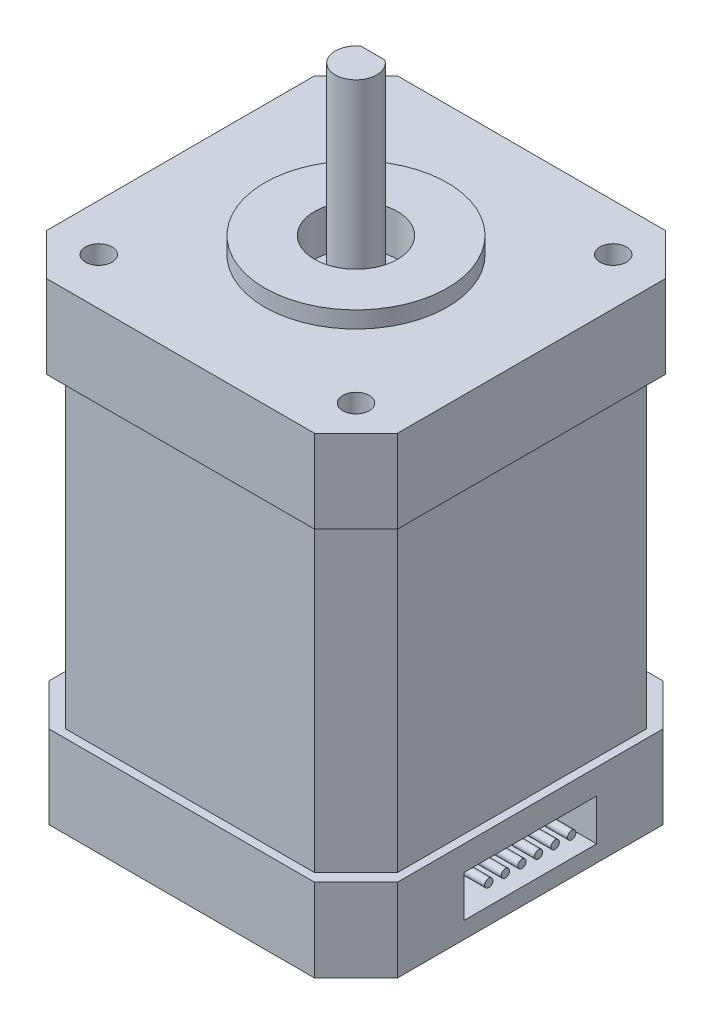
SolidWorks part; units mm, degrees
ref_plane "前视基准面" through (0, 0, 0) normal (0, 0, 1) x (1, 0, 0)
ref_plane "上视基准面" through (0, 0, 0) normal (0, 1, 0) x (1, 0, 0)
ref_plane "右视基准面" through (0, 0, 0) normal (1, 0, 0) x (0, 0, -1)
sketch "草图1" plane through (0, 0, 0) normal (0, 1, 0) x (1, 0, 0)
  line L1 (-21.15, 21.15) -> (21.15, 21.15)
  line L2 (-21.15, 21.15) -> (-21.15, -21.15)
  line L3 (-21.15, -21.15) -> (21.15, -21.15)
  line L4 (21.15, 21.15) -> (21.15, -21.15)
  dimension "D1" = 42.3
  dimension "D2" = 42.3
  dimension "D3" = 21.15
  dimension "D4" = 21.15
extrude "凸台-拉伸1" add sketch "草图1" along normal blind 10
chamfer "倒角1" distance 5 angle 45 4 edges at (-21.15, 5, -21.15) (-21.15, 5, 21.15) (21.15, 5, 21.15) (21.15, 5, -21.15)
sketch "草图2" plane through (0, 10, 0) normal (0, 1, 0) x (1, 0, 0)
  circle A0 centre (-15.5, -15.5) radius 1.6
  circle A1 centre (15.5, -15.5) radius 1.6
  circle A2 centre (15.5, 15.5) radius 1.6
  circle A3 centre (-15.5, 15.5) radius 1.6
  dimension "D1" = 31
  dimension "D2" = 31
extrude "切除-拉伸1" cut sketch "草图2" against normal blind 10
sketch "草图3" plane through (0, 0, 0) normal (0, -1, 0) x (1, 0, 0)
  line L1 (20, 20) -> (-20, 20)
  line L2 (20, 20) -> (20, -20)
  line L3 (20, -20) -> (-20, -20)
  line L4 (-20, 20) -> (-20, -20)
  dimension "D1" = 40
  dimension "D2" = 40
  dimension "D3" = 20
  dimension "D4" = 20
extrude "凸台-拉伸2" add sketch "草图3" along normal blind 37
chamfer "倒角2" distance 5 angle 45 4 edges at (20, -18.5, 20) (-20, -18.5, 20) (-20, -18.5, -20) (20, -18.5, -20)
sketch "草图4" plane through (0, -37, 0) normal (0, -1, 0) x (1, 0, 0)
  line L1 (21, 21) -> (-21, 21)
  line L2 (21, 21) -> (21, -21)
  line L3 (21, -21) -> (-21, -21)
  line L4 (-21, 21) -> (-21, -21)
  dimension "D1" = 42
  dimension "D2" = 42
  dimension "D3" = 21
  dimension "D4" = 21
extrude "凸台-拉伸3" add sketch "草图4" along normal blind 10
chamfer "倒角3" distance 5 angle 45 4 edges at (-21, -42, 21) (21, -42, 21) (21, -42, -21) (-21, -42, -21)
sketch "草图5" plane through (0, 10, 0) normal (0, 1, 0) x (1, 0, 0)
  circle A0 centre (0, 0) radius 11
extrude "凸台-拉伸4" add sketch "草图5" along normal blind 2
sketch "草图6" plane through (0, 12, 0) normal (0, 1, 0) x (1, 0, 0)
  circle A0 centre (0, 0) radius 5
extrude "切除-拉伸2" cut sketch "草图6" against normal blind 5
sketch "草图7" plane through (0, 7, 0) normal (0, 1, 0) x (1, 0, 0)
  line L0 (-1.4339, 2.0479) -> (1.4339, 2.0479)
  arc A0 (-1.4339, 2.0479) -> (1.4339, 2.0479) centre (0, 0) ccw
extrude "凸台-拉伸5" add sketch "草图7" along normal blind 23
sketch "草图8" plane through (0, -47, 0) normal (0, -1, 0) x (1, 0, 0)
  circle A0 centre (0, 0) radius 5
extrude "切除-拉伸3" cut sketch "草图8" against normal blind 3
sketch "草图9" plane through (21, 0, 0) normal (1, 0, 0) x (0, 0, -1)
  line L5 (16, -47) -> (16, -37) construction
  line L6 (-8, -40) -> (8, -40)
  line L8 (-8, -40) -> (-8, -45)
  line L9 (-8, -45) -> (8, -45)
  line L10 (8, -40) -> (8, -45)
  line L11 (16, -47) -> (-16, -47) construction
  point P4 (8, -42.5)
  point P7 (0, -45)
  dimension "D1" = 5
  dimension "D2" = 16
  dimension "D3" = 8
  dimension "D4" = 2
extrude "切除-拉伸5" cut sketch "草图9" against normal blind 5
sketch "草图10" plane through (16, 0, 0) normal (1, 0, 0) x (0, 0, -1)
  line L0 (8, -45) -> (8, -40) construction
  circle A0 centre (-5, -42.5764) radius 0.5
  circle A1 centre (-3, -42.5764) radius 0.5
  circle A2 centre (-1, -42.5764) radius 0.5
  circle A3 centre (1, -42.5764) radius 0.5
  circle A4 centre (3, -42.5764) radius 0.5
  circle A5 centre (5, -42.5764) radius 0.5
  dimension "D1" = 1
  dimension "D2" = 1
  dimension "D3" = 1
  dimension "D4" = 1
  dimension "D5" = 1
  dimension "D6" = 2
  dimension "D7" = 2
  dimension "D8" = 2
  dimension "D9" = 2
  dimension "D10" = 2
  dimension "D11" = 3
extrude "凸台-拉伸6" add sketch "草图10" along normal blind 5
sketch "草图11" plane through (0, -47, 0) normal (0, -1, 0) x (1, 0, 0)
  circle A0 centre (-16, -16) radius 2.5
  circle A1 centre (-16, 16) radius 2.5
  circle A2 centre (16, -16) radius 2.5
  circle A3 centre (16, 16) radius 2.5
  dimension "D3" = 32
extrude "切除-拉伸6" cut sketch "草图11" against normal blind 3
sketch "草图12" plane through (0, -44, 0) normal (0, -1, 0) x (1, 0, 0)
  circle A0 centre (16, -16) radius 2
  circle A1 centre (-16, -16) radius 2
  circle A2 centre (-16, 16) radius 2
  circle A3 centre (16, 16) radius 2
extrude "凸台-拉伸7" add sketch "草图12" along normal blind 2
fillet "圆角3" radius 1 4 edges at (16, -46, 14) (-16, -46, 14) (-16, -46, -18) (16, -46, -18)
sketch "草图13" plane through (0, -46, 0) normal (0, -1, 0) x (1, 0, 0)
  line L28 (17.5049, -16.2012) -> (16.2549, -16.2012)
  line L29 (17.5049, -16.2012) -> (17.5049, -15.7012)
  line L30 (17.5049, -15.7012) -> (16.2549, -15.7012)
  line L31 (14.5049, -16.2012) -> (14.5049, -15.7012)
  line L32 (15.7549, -15.7012) -> (15.7549, -14.4512)
  line L33 (16.2549, -17.4512) -> (15.7549, -17.4512)
  line L34 (16.2549, -17.4512) -> (16.2549, -16.2012)
  line L35 (16.2549, -14.4512) -> (15.7549, -14.4512)
  line L36 (15.7549, -17.4512) -> (15.7549, -16.2012)
  line L37 (16.2549, -15.7012) -> (16.2549, -14.4512)
  line L38 (15.7549, -16.2012) -> (14.5049, -16.2012)
  line L39 (15.7549, -15.7012) -> (14.5049, -15.7012)
  line L40 (-14.5334, -16.2089) -> (-15.7834, -16.2089)
  line L41 (-14.5334, -16.2089) -> (-14.5334, -15.7089)
  line L42 (-14.5334, -15.7089) -> (-15.7834, -15.7089)
  line L43 (-17.5334, -16.2089) -> (-17.5334, -15.7089)
  line L44 (-16.2834, -15.7089) -> (-16.2834, -14.4589)
  line L45 (-15.7834, -17.4589) -> (-16.2834, -17.4589)
  line L46 (-15.7834, -17.4589) -> (-15.7834, -16.2089)
  line L47 (-15.7834, -14.4589) -> (-16.2834, -14.4589)
  line L48 (-16.2834, -17.4589) -> (-16.2834, -16.2089)
  line L49 (-15.7834, -15.7089) -> (-15.7834, -14.4589)
  line L50 (-16.2834, -16.2089) -> (-17.5334, -16.2089)
  line L51 (-16.2834, -15.7089) -> (-17.5334, -15.7089)
  line L52 (-14.4999, 15.7414) -> (-15.7499, 15.7414)
  line L53 (-14.4999, 15.7414) -> (-14.4999, 16.2414)
  line L54 (-14.4999, 16.2414) -> (-15.7499, 16.2414)
  line L55 (-17.4999, 15.7414) -> (-17.4999, 16.2414)
  line L56 (-16.2499, 16.2414) -> (-16.2499, 17.4914)
  line L57 (-15.7499, 14.4914) -> (-16.2499, 14.4914)
  line L58 (-15.7499, 14.4914) -> (-15.7499, 15.7414)
  line L59 (-15.7499, 17.4914) -> (-16.2499, 17.4914)
  line L60 (-16.2499, 14.4914) -> (-16.2499, 15.7414)
  line L61 (-15.7499, 16.2414) -> (-15.7499, 17.4914)
  line L62 (-16.2499, 15.7414) -> (-17.4999, 15.7414)
  line L63 (-16.2499, 16.2414) -> (-17.4999, 16.2414)
  line L64 (17.4764, 15.7556) -> (16.2264, 15.7556)
  line L65 (17.4764, 15.7556) -> (17.4764, 16.2556)
  line L66 (17.4764, 16.2556) -> (16.2264, 16.2556)
  line L67 (14.4764, 15.7556) -> (14.4764, 16.2556)
  line L68 (15.7264, 16.2556) -> (15.7264, 17.5056)
  line L69 (16.2264, 14.5056) -> (15.7264, 14.5056)
  line L70 (16.2264, 14.5056) -> (16.2264, 15.7556)
  line L71 (16.2264, 17.5056) -> (15.7264, 17.5056)
  line L72 (15.7264, 14.5056) -> (15.7264, 15.7556)
  line L73 (16.2264, 16.2556) -> (16.2264, 17.5056)
  line L74 (15.7264, 15.7556) -> (14.4764, 15.7556)
  line L75 (15.7264, 16.2556) -> (14.4764, 16.2556)
  point P20 (16.0049, -14.4512)
  point P23 (14.5049, -15.9512)
  point P34 (-16.0334, -14.4589)
  point P37 (-17.5334, -15.9589)
  point P48 (-15.9999, 17.4914)
  point P51 (-17.4999, 15.9914)
  point P62 (15.9764, 17.5056)
  point P65 (14.4764, 16.0056)
  dimension "D7" = 3
  dimension "D8" = 0.5
  dimension "D9" = 3
  dimension "D10" = 0.5
  dimension "D11" = 1.25
  dimension "D12" = 1.25
  dimension "D13" = 3
  dimension "D14" = 0.5
  dimension "D15" = 3
  dimension "D16" = 0.5
  dimension "D17" = 1.25
  dimension "D18" = 1.25
  dimension "D19" = 3
  dimension "D20" = 0.5
  dimension "D21" = 3
  dimension "D22" = 0.5
  dimension "D23" = 1.25
  dimension "D24" = 1.25
  dimension "D25" = 3
  dimension "D26" = 0.5
  dimension "D27" = 3
  dimension "D28" = 0.5
  dimension "D29" = 1.25
  dimension "D30" = 1.25
extrude "切除-拉伸7" cut sketch "草图13" against normal blind 1
scale "缩放比例1" scale about centroid uniform scaling yes scale factor 2
